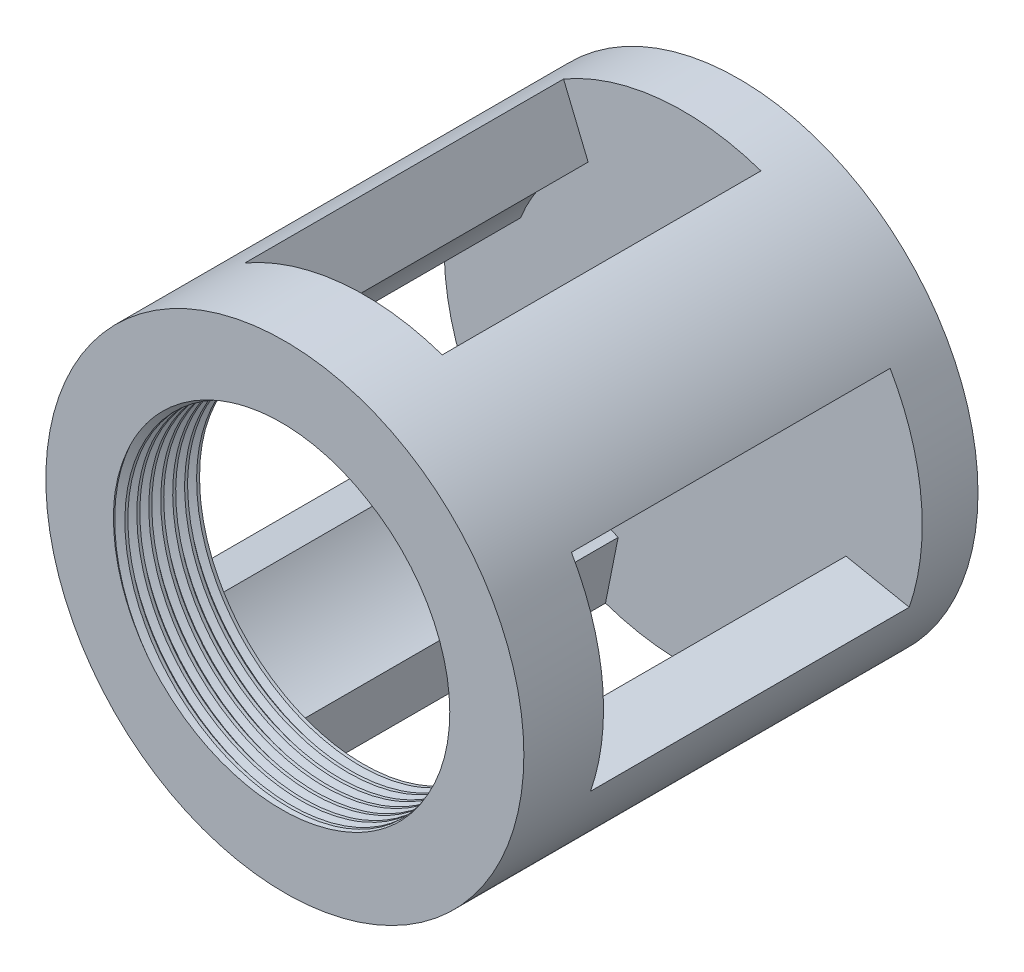
SolidWorks part; units mm, degrees
other "Markup1"
sketch "Sketch7" plane through (30, -30, 57) normal (0.4912, -0.8106, 0.3189) x (-0.0913, -0.4119, -0.9066)
ref_plane "Front Plane" through (0, 0, 0) normal (0, 0, 1) x (1, 0, 0)
ref_plane "Top Plane" through (0, 0, 0) normal (0, 1, 0) x (1, 0, 0)
ref_plane "Right Plane" through (0, 0, 0) normal (1, 0, 0) x (0, 0, -1)
sketch "Sketch1" plane through (0, 0, 0) normal (0, 0, 1) x (1, 0, 0)
  circle A0 centre (0, 0) radius 30
  circle A1 centre (0, 0) radius 4
  dimension "D1" = 60
  dimension "D2" = 8
extrude "Boss-Extrude1" add sketch "Sketch1" along normal blind 7
sketch "Sketch3" plane through (0, 0, 7) normal (0, 0, 1) x (1, 0, 0)
  circle A0 centre (0, 19.5) radius 2.25
  circle A1 centre (19.5, 0) radius 2.25
  circle A2 centre (0, -19.5) radius 2.25
  circle A3 centre (-19.5, 0) radius 2.25
  point P12 (0, 0)
  dimension "D1" = 4.5
  dimension "D2" = 19.5
  dimension "D3" = 4
sketch "Sketch5" plane through (0, 0, 7) normal (0, 0, 1) x (1, 0, 0)
  line L0 (-28.3698, 9.7548) -> (-20.4279, 8.167)
  line L1 (-15.0173, 25.9708) -> (-11.935, 18.4812)
  line L2 (0, 0) -> (-1.8144, 3.5648) construction
  line L3 (25.9708, 15.0173) -> (18.4812, 11.935)
  line L4 (9.7548, 28.3698) -> (8.167, 20.4279)
  line L5 (15.0173, -25.9708) -> (11.935, -18.4812)
  line L6 (28.3698, -9.7548) -> (20.4279, -8.167)
  line L7 (-25.9708, -15.0173) -> (-18.4812, -11.935)
  line L8 (-9.7548, -28.3698) -> (-8.167, -20.4279)
  arc A0 (-28.3698, 9.7548) -> (-15.0173, 25.9708) centre (0, 0) cw
  circle A1 centre (0, 0) radius 30 construction
  arc A2 (-20.4279, 8.167) -> (-11.935, 18.4812) centre (0, 0) cw
  circle A3 centre (0, 0) radius 4 construction
  arc A4 (9.7548, 28.3698) -> (25.9708, 15.0173) centre (0, 0) cw
  arc A5 (8.167, 20.4279) -> (18.4812, 11.935) centre (0, 0) cw
  arc A6 (28.3698, -9.7548) -> (15.0173, -25.9708) centre (0, 0) cw
  arc A7 (20.4279, -8.167) -> (11.935, -18.4812) centre (0, 0) cw
  arc A8 (-9.7548, -28.3698) -> (-25.9708, -15.0173) centre (0, 0) cw
  arc A9 (-8.167, -20.4279) -> (-18.4812, -11.935) centre (0, 0) cw
  point P8 (-23.1592, 19.0696)
  point P9 (-16.9834, 13.9844)
  point P28 (0, 0)
  dimension "D3" = 4
  dimension "D1" = 8
extrude "Boss-Extrude2" add sketch "Sketch5" along normal blind 40
sketch "Sketch6" plane through (0, 0, 47) normal (0, 0, 1) x (1, 0, 0)
  circle A0 centre (0, 0) radius 30
  circle A1 centre (0, 0) radius 20.701
  dimension "D1" = 41.402
  dimension "D2" = 60
extrude "Boss-Extrude3" add sketch "Sketch6" along normal blind 10
thread "Thread1" pitch 1.5 method cut profile "Thread Profile1" start angle 0, offset 2, length 0, pitch 1.5, diameter 41.402
ref_plane "Plane1" through (-20.701, 0, 59) normal (0, -1, 0) x (-1, 0, 0)
sketch "Thread Profile1" plane through (-20.701, 0, 59) normal (0, -1, 0) x (-1, 0, 0)
  line L0 (0, 0) -> (0, 1.5) construction
  line L1 (0, 0) -> (0.8119, 0.4687)
  line L2 (0.8119, 0.4687) -> (0.8119, 0.6562)
  line L3 (0.8119, 0.6562) -> (0, 1.125)
  line L4 (0.8119, 0.5625) -> (0, 0.5625) construction
  line L11 (0, 0) -> (0, 1.125)
  point P2 (0, 0)
  dimension "Pitch" = 1.5
  dimension "Profile_Angle" = 60
  dimension "Profile_Land" = 0.1875
  dimension "Profile_Height" = 0.8119
